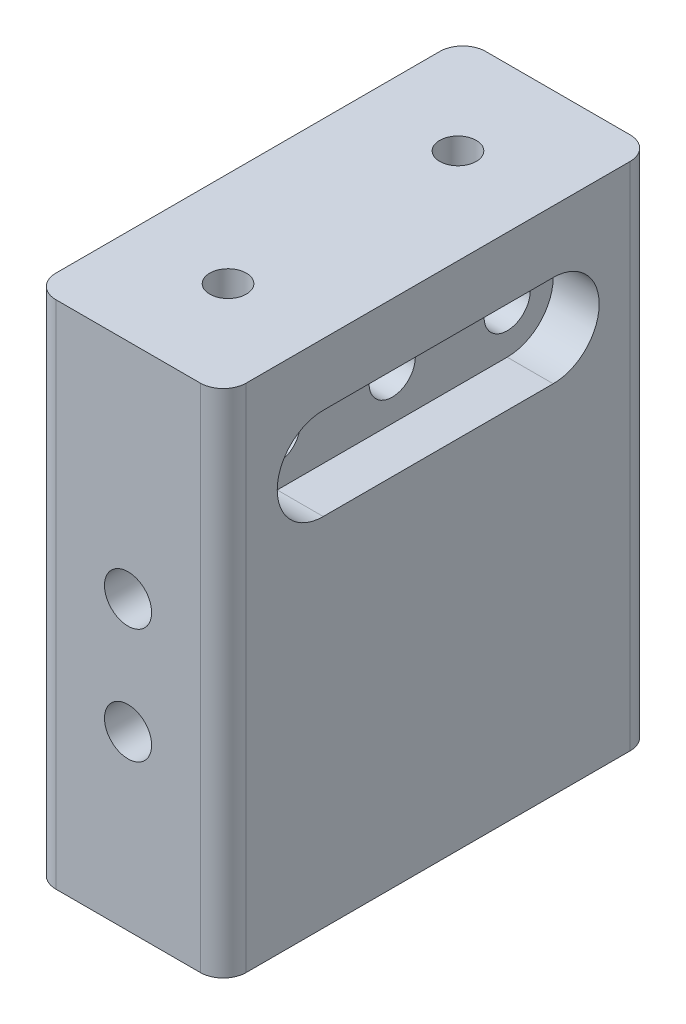
SolidWorks part; units mm, degrees
ref_plane "Front Plane" through (0, 0, 0) normal (0, 0, 1) x (1, 0, 0)
ref_plane "Top Plane" through (0, 0, 0) normal (0, 1, 0) x (1, 0, 0)
ref_plane "Right Plane" through (0, 0, 0) normal (1, 0, 0) x (0, 0, -1)
sketch "Sketch1" plane through (0, 0, 0) normal (0, 1, 0) x (1, 0, 0)
  line L1 (-10.5156, -23.7427) -> (10.5156, -23.7427)
  line L2 (-10.5156, -23.7427) -> (-10.5156, 23.7426)
  line L3 (-10.5156, 23.7426) -> (10.5156, 23.7426)
  line L4 (10.5156, -23.7427) -> (10.5156, 23.7426)
  line L5 (-10.5156, -23.7427) -> (10.5156, 23.7426) construction
  line L6 (-10.5156, 23.7426) -> (10.5156, -23.7427) construction
  point P0 (0, 0)
  dimension "D1" = 21.0312
  dimension "D2" = 47.4853
extrude "Boss-Extrude1" add sketch "Sketch1" along normal mid plane 50.8
sketch "Sketch2" plane through (0, 0, 23.7427) normal (0, 0, 1) x (1, 0, 0)
  line L4 (-10.5156, 25.4) -> (-10.5156, -25.4) construction
  line L5 (-10.5156, 25.4) -> (10.5156, 25.4) construction
  circle A1 centre (0, -6.35) radius 2.6035
  circle A2 centre (0, 6.35) radius 2.6035
  dimension "D3" = 19.05
  dimension "D1" = 10.5156
  dimension "D2" = 5.207
  dimension "D4" = 12.7
extrude "Cut-Extrude1" cut sketch "Sketch2" against normal through all
sketch "Sketch4" plane through (10.5156, 0, 0) normal (1, 0, 0) x (0, 0, -1)
  line L0 (-23.7427, 25.4) -> (23.7426, 25.4) construction
  circle A0 centre (-12.7, 19.05) radius 2.5527
  circle A1 centre (12.7, 19.05) radius 2.5527
  circle A2 centre (0, 19.05) radius 2.5527
  dimension "D5" = 5.1054
  dimension "D1" = 6.35
  dimension "D3" = 12.7
  dimension "D4" = 12.7
extrude "Cut-Extrude3" cut sketch "Sketch4" against normal through all
fillet "Fillet1" radius 2.54 4 edges at (10.5156, 0, 23.7427) (-10.5156, 0, 23.7427) (-10.5156, 0, -23.7426) (10.5156, 0, -23.7426)
sketch "Sketch7" plane through (10.5156, 0, 0) normal (1, 0, 0) x (0, 0, -1)
  line L0 (-12.7, 19.05) -> (12.7, 19.05) construction
  line L1 (-12.7, 24.13) -> (12.7, 24.13)
  line L2 (-12.7, 13.97) -> (12.7, 13.97)
  arc A0 (-12.7, 24.13) -> (-12.7, 13.97) centre (-12.7, 19.05) ccw
  arc A1 (12.7, 13.97) -> (12.7, 24.13) centre (12.7, 19.05) ccw
  point P4 (0, 19.05)
  dimension "D1" = 5.08
extrude "Cut-Extrude5" cut sketch "Sketch7" against normal blind 5.08
sketch "Sketch8" plane through (0, 25.4, 0) normal (0, 1, 0) x (1, 0, 0)
  line L4 (-7.9756, -23.7427) -> (7.9756, -23.7427)
  line L5 (10.5156, -21.2026) -> (10.5156, 21.2026)
  line L6 (7.9756, 23.7426) -> (-7.9756, 23.7426)
  line L7 (-10.5156, 21.2026) -> (-10.5156, -21.2026)
  line L8 (-7.9756, -23.7427) -> (7.9756, -23.7427)
  line L9 (10.5156, -21.2026) -> (10.5156, 21.2026)
  line L10 (7.9756, 23.7426) -> (-7.9756, 23.7426)
  line L11 (-10.5156, 21.2026) -> (-10.5156, -21.2026)
  arc A4 (7.9756, -23.7427) -> (10.5156, -21.2026) centre (7.9756, -21.2026) ccw
  arc A5 (10.5156, 21.2026) -> (7.9756, 23.7426) centre (7.9756, 21.2026) ccw
  arc A6 (-7.9756, 23.7426) -> (-10.5156, 21.2026) centre (-7.9756, 21.2026) ccw
  arc A7 (-10.5156, -21.2026) -> (-7.9756, -23.7427) centre (-7.9756, -21.2026) ccw
  arc A8 (7.9756, -23.7427) -> (10.5156, -21.2026) centre (7.9756, -21.2026) ccw
  arc A9 (10.5156, 21.2026) -> (7.9756, 23.7426) centre (7.9756, 21.2026) ccw
  arc A10 (-7.9756, 23.7426) -> (-10.5156, 21.2026) centre (-7.9756, 21.2026) ccw
  arc A11 (-10.5156, -21.2026) -> (-7.9756, -23.7427) centre (-7.9756, -21.2026) ccw
  dimension "D1" = 0
extrude "Boss-Extrude2" add sketch "Sketch8" along normal blind 5.588
sketch "Sketch9" plane through (0, 30.988, 0) normal (0, 1, 0) x (1, 0, 0)
  line L0 (-10.5156, 0) -> (10.5156, 0) construction
  line L1 (-10.5156, 21.2026) -> (-10.5156, -21.2026) construction
  line L2 (10.5156, -21.2026) -> (10.5156, 21.2026) construction
  circle A0 centre (0, 12.7) radius 2.0193
  circle A2 centre (0, -12.7) radius 2.0193
  dimension "D2" = 4.0386
  dimension "D1" = 12.7
  dimension "D3" = 10.5156
extrude "Cut-Extrude6" cut sketch "Sketch9" against normal blind 5.08
